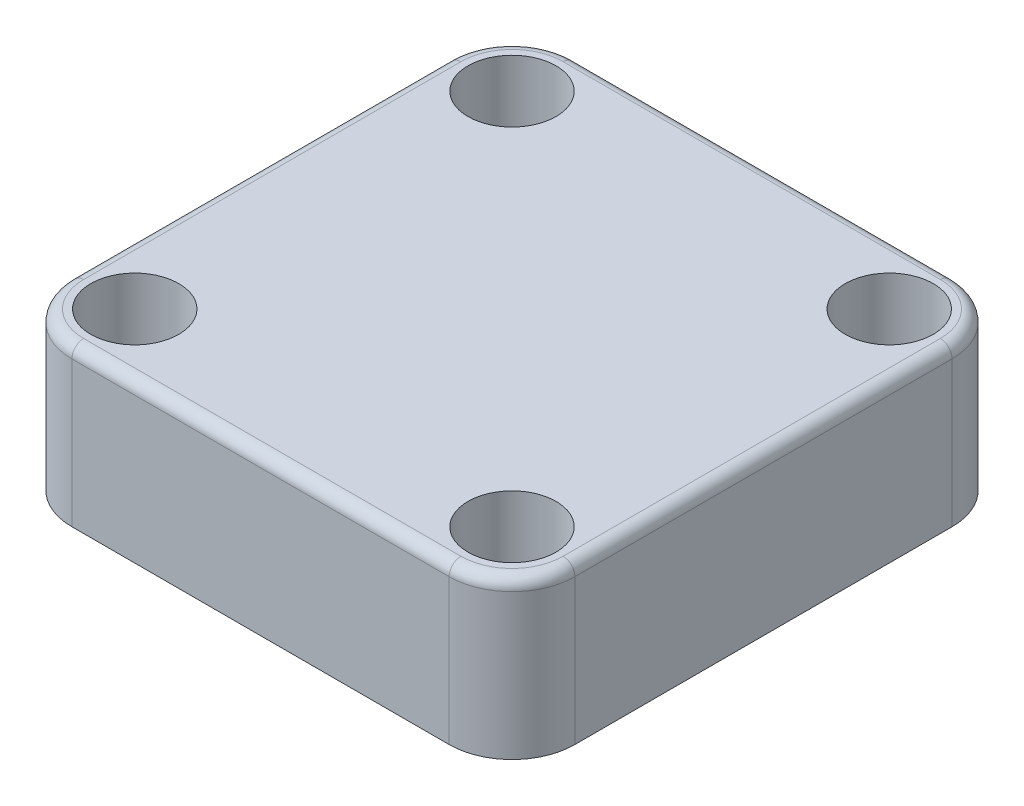
SolidWorks part; units mm, degrees
ref_plane "Front Plane" through (0, 0, 0) normal (0, 0, 1) x (1, 0, 0)
ref_plane "Top Plane" through (0, 0, 0) normal (0, 1, 0) x (1, 0, 0)
ref_plane "Right Plane" through (0, 0, 0) normal (1, 0, 0) x (0, 0, -1)
sketch "Sketch1" plane through (0, 0, 0) normal (0, 1, 0) x (1, 0, 0)
  line L0 (-16, 12) -> (-16, -12)
  line L1 (-12, 12) -> (12, 12)
  line L2 (-12, 12) -> (-12, -12)
  line L3 (-12, -12) -> (12, -12)
  line L4 (12, 12) -> (12, -12)
  line L5 (-12, 12) -> (12, -12) construction
  line L6 (-12, -12) -> (12, 12) construction
  line L7 (-12, -16) -> (12, -16)
  line L8 (16, 12) -> (16, -12)
  line L9 (-12, 16) -> (12, 16)
  circle A0 centre (-12, 12) radius 1.6
  circle A1 centre (12, 12) radius 1.6
  circle A2 centre (12, -12) radius 1.6
  circle A3 centre (-12, -12) radius 1.6
  circle A4 centre (-12, 12) radius 4
  circle A5 centre (12, 12) radius 4
  circle A6 centre (12, -12) radius 4
  circle A7 centre (-12, -12) radius 4
  point P0 (0, 0)
  point P22 (12, 16)
  dimension "D2" = 3.2
  dimension "D3" = 8
  dimension "D1" = 24
extrude "Boss-Extrude1" add sketch "Sketch1" along normal blind 10 contours A5 L9 A4 L1 | L1 A4 L2 A0 | A7 L2 A4 L0 | A7 L3 A3 L2 | A7 L7 A6 L3 | A6 L4 A2 L3 | A6 L8 A5 L4 | A7 L3 A6 L4 A5 L1 A4 L2 | L4 A6 L3 A2 | L3 A7 L2 A3 | L2 A4 L1 A0 | L4 A5 L1 A1 | L1 A5 L4 A1 region at (-14.1072, 0, 0) region at (-14.7484, 0, -14.7484) region at (-14.7484, 0, 9.2516) region at (0, 0, -14.1072) region at (0, 0, 0) region at (-10.1083, 0, -10.1083) region at (0, 0, 14.1072) region at (-10.1083, 0, 10.1083) region at (14.7484, 0, -14.7484) region at (9.2516, 0, 14.7484) region at (14.1072, 0, 0) region at (10.1083, 0, -10.1083) region at (10.1083, 0, 10.1083)
sketch "Sketch2" plane through (0, 0, 0) normal (0, -1, 0) x (1, 0, 0)
  line L0 (-12, 16) -> (12, 16) construction
  line L1 (8, -16) -> (-8, -16)
  line L2 (8, -16) -> (8, 16)
  line L3 (8, 16) -> (-8, 16)
  line L4 (-8, -16) -> (-8, 16)
  line L5 (8, -16) -> (-8, 16) construction
  line L6 (8, 16) -> (-8, -16) construction
  circle A0 centre (0, 0) radius 14
  circle A3 centre (-12, 12) radius 1.6 construction
  circle A4 centre (-12, 12) radius 1.6
  point P10 (0, 0)
  line M12 (-12, -16) -> (12, -16)
  dimension "D1" = 28
  dimension "D2" = 4
extrude "Cut-Extrude1" cut sketch "Sketch2" against normal offset from surface (8.5 mm away) 1.5 contours A0 L4 L2 M12 | A0 region at (0, 0, -14.5009) up to face at (-12, 10, 13.6)
sketch "Sketch3" plane through (0, 10, 0) normal (0, 1, 0) x (1, 0, 0)
  circle A0 centre (-12, 12) radius 2.8
  circle A1 centre (12, 12) radius 2.8
  circle A2 centre (12, -12) radius 2.8
  circle A3 centre (-12, -12) radius 2.8
  dimension "D1" = 5.6
extrude "Cut-Extrude2" cut sketch "Sketch3" against normal offset from surface (8 mm away) 2 up to face at (0, 0, -2.4574)
fillet "Fillet1" radius 3 2 edges at (-8, 4.25, -11.4891) (8, 4.25, -11.4891)
fillet "Fillet2" radius 3 5 edges at (8, 8.5, -14.4807) (8.2775, 8.5, -11.7012) (-8, 8.5, -14.4807) (-8.2775, 8.5, -11.7012) (0, 8.5, 14)
fillet "Fillet3" radius 0.75 8 edges at (-14.8284, 10, 14.8284) (-16, 10, 0) (-14.8284, 10, -14.8284) (0, 10, -16) (14.8284, 10, -14.8284) (16, 10, 0) (14.8284, 10, 14.8284) (0, 10, 16)
